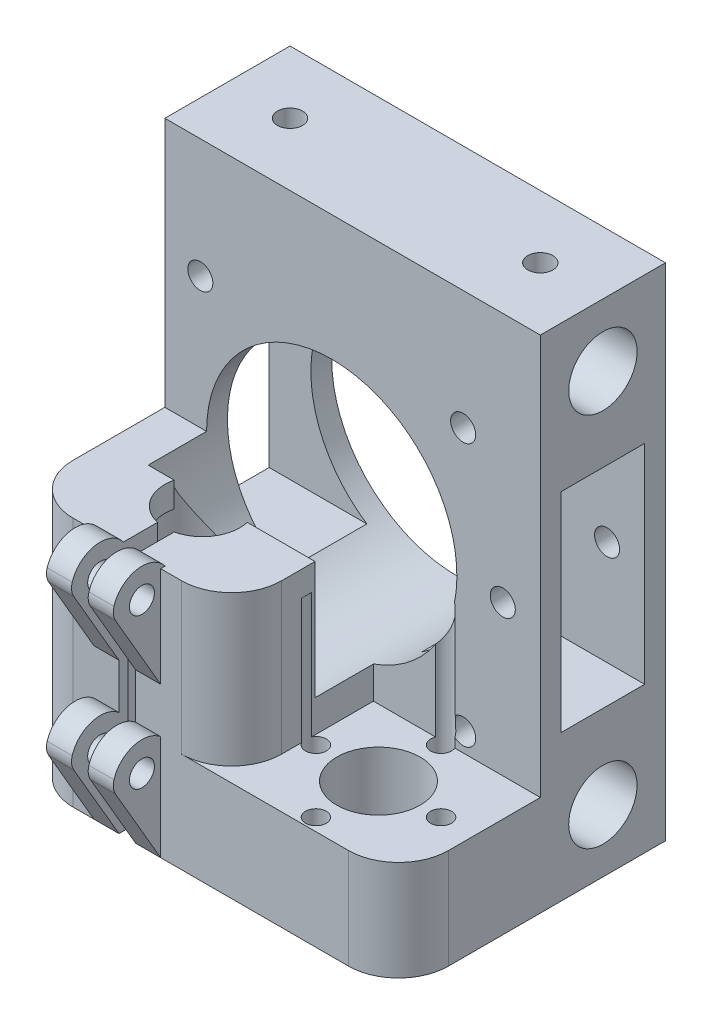
SolidWorks part; units mm, degrees
ref_plane "Front Plane" through (0, 0, 0) normal (0, 0, 1) x (1, 0, 0)
ref_plane "Top Plane" through (0, 0, 0) normal (0, 1, 0) x (1, 0, 0)
ref_plane "Right Plane" through (0, 0, 0) normal (1, 0, 0) x (0, 0, -1)
sketch "Sketch1" plane through (0, 0, 0) normal (0, 0, 1) x (1, 0, 0)
  line L1 (-22.5, -30) -> (22.5, -30)
  line L2 (-22.5, -30) -> (-22.5, 30)
  line L3 (-22.5, 30) -> (22.5, 30)
  line L4 (22.5, -30) -> (22.5, 30)
  line L5 (-22.5, -30) -> (22.5, 30) construction
  line L6 (-22.5, 30) -> (22.5, -30) construction
  point P0 (0, 0)
  dimension "D1" = 45
  dimension "D2" = 60
extrude "Boss-Extrude1" add sketch "Sketch1" along normal blind 15
sketch "Sketch2" plane through (22.5, 0, 0) normal (1, 0, 0) x (0, 0, -1)
  line L0 (-7.5, 30) -> (-7.5, -30) construction
  line L1 (-15, 30) -> (0, 30) construction
  line L2 (-15, -30) -> (0, -30) construction
  line L3 (0, -30) -> (0, 30) construction
  line L4 (-12.5, -12.5) -> (-2.5, -12.5)
  line L5 (-12.5, -12.5) -> (-12.5, 12.5)
  line L6 (-12.5, 12.5) -> (-2.5, 12.5)
  line L7 (-2.5, -12.5) -> (-2.5, 12.5)
  line L8 (-12.5, -12.5) -> (-2.5, 12.5) construction
  line L9 (-12.5, 12.5) -> (-2.5, -12.5) construction
  line L10 (-15, 0) -> (0, 0) construction
  line L11 (-15, -30) -> (-15, 30) construction
  circle A0 centre (-7.5, 22.5) radius 4.1
  circle A1 centre (-7.5, -22.5) radius 4.1
  point P6 (-7.5, 0)
  dimension "D3" = 8.2
  dimension "D1" = 2.5
  dimension "D2" = 25
  dimension "D4" = 22.5
extrude "Cut-Extrude1" cut sketch "Sketch2" against normal through all
sketch "Sketch3" plane through (-22.5, 0, 0) normal (-1, 0, 0) x (0, 0, 1)
  line L1 (15, -30) -> (32, -30)
  line L2 (15, -30) -> (15, -18)
  line L3 (15, -18) -> (32, -18)
  line L4 (32, -30) -> (32, -18)
  dimension "D1" = 17
  dimension "D2" = 12
extrude "Boss-Extrude2" add sketch "Sketch3" against normal up to surface (45 mm away) up to face at (22.5, -22.5, 11.6)
sketch "Sketch4" plane through (0, -18, 0) normal (0, 1, 0) x (1, 0, 0)
  line L1 (-22.5, -32) -> (2.5, -32)
  line L2 (2.5, -15) -> (-22.5, -15)
  line L7 (-22.5, -15) -> (-22.5, -32)
  line L9 (2.5, -15) -> (2.5, -32)
  dimension "D1" = 17
  dimension "D2" = 25
extrude "Boss-Extrude3" add sketch "Sketch4" along normal blind 18
sketch "Sketch5" plane through (0, 0, 32) normal (0, 0, 1) x (1, 0, 0)
  line L0 (-10, 0) -> (-10, -30) construction
  line L1 (2.5, 0) -> (-22.5, 0) construction
  line L2 (22.5, -30) -> (-22.5, -30) construction
  line L4 (-11, -30) -> (-9, -30)
  line L5 (-11, -30) -> (-11, 0)
  line L6 (-11, 0) -> (-9, 0)
  line L7 (-9, -30) -> (-9, 0)
  line L8 (-11, -30) -> (-9, 0) construction
  line L9 (-11, 0) -> (-9, -30) construction
  point P6 (-10, -15)
  dimension "D1" = 2
  dimension "D2" = 30
extrude "Cut-Extrude2" cut sketch "Sketch5" against normal blind 5
sketch "Sketch6" plane through (0, -30, 0) normal (0, -1, 0) x (1, 0, 0)
  line L0 (-10, 27) -> (-10, 15) construction
  line L1 (-9, 27) -> (-11, 27) construction
  line L2 (2.5, 15) -> (-22.5, 15) construction
  circle A0 centre (-10, 23) radius 4.5
  dimension "D1" = 9
  dimension "D2" = 4
extrude "Cut-Extrude3" cut sketch "Sketch6" against normal through all
sketch "Sketch7" plane through (0, -30, 0) normal (0, -1, 0) x (1, 0, 0)
  line L0 (-10, 23) -> (-22.5, 23) construction
  line L1 (-22.5, 32) -> (-22.5, 0) construction
  line L2 (11.1, 23) -> (14.6355, 26.5355) construction
  line L3 (11.1, 23) -> (11.1, 30.5) construction
  line L4 (11.1, 23) -> (14.6355, 19.4645) construction
  circle A0 centre (-10, 23) radius 8
  circle A1 centre (11.1, 23) radius 5
  circle A2 centre (18.6, 23) radius 1.25
  circle A3 centre (11.1, 30.5) radius 1.25
  circle A4 centre (11.1, 15.5) radius 1.25
  circle A5 centre (3.6, 23) radius 1.25
  dimension "D1" = 16
  dimension "D2" = 10
  dimension "D4" = 2.5
  dimension "D8" = 2.5
  dimension "D3" = 21.1
  dimension "D5" = 7.5
  dimension "D6" = 45
  dimension "D7" = 7.5
  dimension "D9" = 45
extrude "Cut-Extrude4" cut sketch "Sketch7" against normal offset from surface (27 mm away) 3 up to face at (-10, 0, 25.4859)
sketch "Sketch8" plane through (0, 0, 0) normal (0, 0, -1) x (-1, 0, 0)
  line L0 (2.5, -30) -> (2.5, 30) construction
  line L3 (-22.5, 0) -> (22.5, 0) construction
  line L4 (-22.5, -30) -> (-22.5, 30) construction
  line L5 (22.5, 30) -> (22.5, -30) construction
  line L6 (2.5, 0) -> (18.25, 15.75) construction
  line L7 (22.5, -30) -> (-22.5, -30) construction
  line L8 (-22.5, 30) -> (22.5, 30) construction
  line L9 (-13.25, -15.75) -> (2.5, 0) construction
  line L10 (18.25, -15.75) -> (2.5, 0) construction
  line L11 (2.5, 0) -> (-13.25, 15.75) construction
  circle A0 centre (2.5, 0) radius 15
  circle A1 centre (18.25, 15.75) radius 1.5
  circle A2 centre (-13.25, 15.75) radius 1.5
  circle A3 centre (-13.25, -15.75) radius 1.5
  circle A4 centre (18.25, -15.75) radius 1.5
  dimension "D1" = 30
  dimension "D2" = 3
  dimension "D10" = 3
  dimension "D3" = 0
  dimension "D4" = 45
  dimension "D5" = 31.5
  dimension "D6" = 31.5
  dimension "D7" = 20
  dimension "D8" = 45
  dimension "D9" = 45
extrude "Cut-Extrude5" cut sketch "Sketch8" against normal blind 22
fillet "Fillet1" radius 6 3 edges at (-22.5, -15, 32) (22.5, -24, 32) (2.5, -9, 32)
sketch "Sketch9" plane through (0, 0, 0) normal (0, 0, -1) x (-1, 0, 0)
  line L0 (-22.5, 0) -> (-12.5, 0) construction
  line L1 (-22.5, -30) -> (-22.5, 30) construction
  circle A0 centre (2.5, 0) radius 15 construction
  circle A1 centre (-18, 0) radius 1.5
  dimension "D1" = 3
  dimension "D2" = 4.5
extrude "Cut-Extrude6" cut sketch "Sketch9" against normal up to surface (15 mm away) up to face at (11.75, 15.75, 15)
sketch "Sketch10" plane through (0, 30, 0) normal (0, 1, 0) x (1, 0, 0)
  line L0 (-22.5, -7.5) -> (22.5, -7.5) construction
  line L1 (-22.5, -15) -> (-22.5, 0) construction
  line L2 (22.5, -15) -> (22.5, 0) construction
  line L3 (0, -15) -> (0, 0) construction
  line L4 (22.5, -15) -> (-22.5, -15) construction
  circle A0 centre (-15, -7.5) radius 1.5
  circle A1 centre (15, -7.5) radius 1.5
  dimension "D1" = 3
  dimension "D2" = 15
extrude "Cut-Extrude7" cut sketch "Sketch10" against normal up to next
extrude "Cut-Extrude8" cut sketch "Sketch10<2>" along normal up to next from surface starting at face at (3.6, -30, 24.25)
sketch "Sketch10<2>" plane through (0, 30, 0) normal (0, 1, 0) x (1, 0, 0) same geometry as "Sketch10"
sketch "Sketch11" plane through (-11, 0, 0) normal (1, 0, 0) x (0, 0, -1)
  line L0 (-32, -30) -> (-37.75, -20.1131)
  line L1 (-30.9373, -18.9837) -> (-30.9373, -30)
  line L2 (-32, -30) -> (-32, -18) construction
  line L3 (-30.9373, -30) -> (-30.9373, -3) construction
  line L4 (-32, -30) -> (-30.9373, -30)
  line L5 (-32, -12) -> (-37.75, -2.1131)
  line L6 (-30.9373, -0.9837) -> (-30.9373, -12)
  line L7 (-32, -12) -> (-30.9373, -12)
  circle A0 centre (-34.25, -20.1131) radius 1.5
  arc A1 (-30.9373, -18.9837) -> (-37.75, -20.1131) centre (-34.25, -20.1131) ccw
  arc A2 (-30.9373, -0.9837) -> (-37.75, -2.1131) centre (-34.25, -2.1131) ccw
  circle A3 centre (-34.25, -2.1131) radius 1.5
  point P7 (-32, -24)
  dimension "D1" = 3
  dimension "D2" = 2
  dimension "D3" = 2.25
  dimension "D5" = 0
  dimension "D6" = 2
extrude "Boss-Extrude4" add sketch "Sketch11" against normal blind 3
extrude "Boss-Extrude6" add sketch "Sketch11<2>" along normal blind 3 from offset 2
sketch "Sketch11<2>" plane through (-11, 0, 0) normal (1, 0, 0) x (0, 0, -1) same geometry as "Sketch11"
fillet "Fillet3" radius 2 4 edges at (-12.5, -2.1131, 37.75) (-7.5, -2.1131, 37.75) (-12.5, -20.1131, 37.75) (-7.5, -20.1131, 37.75)
